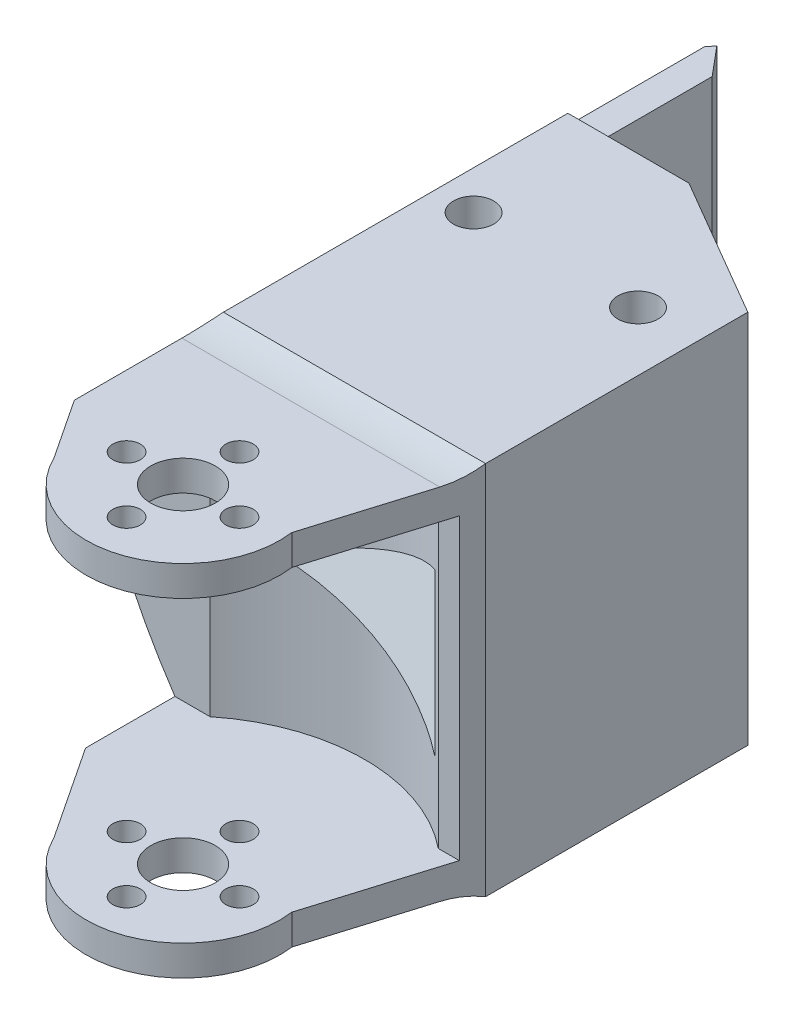
SolidWorks part; units mm, degrees
ref_plane "Front Plane" through (0, 0, 0) normal (0, 0, 1) x (1, 0, 0)
ref_plane "Top Plane" through (0, 0, 0) normal (0, 1, 0) x (1, 0, 0)
ref_plane "Right Plane" through (0, 0, 0) normal (1, 0, 0) x (0, 0, -1)
sketch "Sketch2" plane through (0, 0, 0) normal (0, 1, 0) x (1, 0, 0)
  line L0 (17.5, 0) -> (17.5, 37.7)
  line L1 (-15, 2.5) -> (15, 2.5)
  line L2 (-15, 2.5) -> (-15, 37.7)
  line L4 (15, 2.5) -> (15, 37.7)
  line L5 (17.5, 37.7) -> (15, 37.7)
  line L7 (-17.5, 37.7) -> (-17.5, 0)
  line L8 (-17.5, 0) -> (17.5, 0)
  line L10 (-17.5, 37.7) -> (-15, 37.7)
  point P4 (0, 2.5)
  point P12 (0, 0)
  dimension "D1" = 2.5
  dimension "D2" = 2.5
  dimension "D3" = 37.7
  dimension "D4" = 30
  dimension "D5" = 15
extrude "Boss-Extrude1" add sketch "Sketch2" along normal blind 32.5
sketch "Sketch4" plane through (0, 0, 0) normal (0, -1, 0) x (1, 0, 0)
  line L0 (-17.5, 0) -> (-17.5, -7.4438)
  line L8 (17.5, -7.4438) -> (17.5, 0)
  line L9 (17.5, 0) -> (-17.5, 0)
  line L10 (17.5, 0) -> (17.5, -37.7) construction
  line L13 (-17.5, -7.4438) -> (-17.5, -37.7)
  line L23 (-17.5, -37.7) -> (-15, -37.7)
  line L34 (-15, -37.7) -> (-15, -7.5)
  line L35 (-15, -2.5) -> (-15, -37.7) construction
  line L36 (-15, -7.5) -> (15, -7.5)
  line L37 (15, -37.7) -> (15, -2.5) construction
  line L38 (15, -7.5) -> (15, -37.7)
  line L39 (15, -37.7) -> (17.5, -37.7)
  line L40 (17.5, -37.7) -> (17.5, -7.4438)
  circle A2 centre (-10.1889, -4.95) radius 1.05
  circle A5 centre (10.1889, -4.95) radius 1.05
  dimension "D5" = 2.1
  dimension "D1" = 7.5
  dimension "D6" = 7.3111
  dimension "D7" = 4.95
  dimension "D8" = 7.3111
extrude "Boss-Extrude2" add sketch "Sketch4" along normal blind 2
sketch "Sketch7" plane through (0, -2, 0) normal (0, -1, 0) x (1, 0, 0)
  line L0 (-17.5, 0) -> (-17.5, -37.7)
  line L1 (-17.5, -37.7) -> (-15, -37.7)
  line L2 (-17.5, 0) -> (17.5, 0)
  line L4 (17.5, 0) -> (17.5, -37.7)
  line L5 (17.5, -37.7) -> (15, -37.7)
  line L6 (15, -37.7) -> (15, -7.5)
  line L7 (15, -7.5) -> (-15, -7.5)
  line L8 (-15, -7.5) -> (-15, -37.7)
  circle A2 centre (-10.1889, -4.95) radius 2.495
  circle A3 centre (10.1889, -4.95) radius 2.495
  dimension "D1" = 4.99
extrude "Wire spacing2" add sketch "Sketch7" along normal blind 3
sketch "Sketch8" plane through (0, -5, 0) normal (0, -1, 0) x (1, 0, 0)
  line L0 (-17.5, 0) -> (-17.5, -37.7)
  line L1 (-17.5, -37.7) -> (17.5, -37.7)
  line L2 (17.5, -37.7) -> (17.5, 0) construction
  line L3 (15, -37.7) -> (17.5, -37.7) construction
  line L4 (-17.5, 0) -> (17.5, 0)
  line L6 (17.5, 0) -> (17.5, -37.7)
  circle A0 centre (-10.1889, -4.95) radius 2.495
  circle A1 centre (10.1889, -4.95) radius 2.495
  circle A2 centre (10.1889, -4.95) radius 2.495 construction
  circle A3 centre (-10.1889, -4.95) radius 2.495 construction
extrude "Boss-Extrude6" add sketch "Sketch8" along normal blind 2
sketch "Sketch5" plane through (0, 32.5, 0) normal (0, 1, 0) x (1, 0, 0)
  line L0 (-7.439, 10) -> (-7.439, 2.5)
  line L9 (15, 2.5) -> (-15, 2.5) construction
  line L11 (-10.1889, 12) -> (-7.439, 10)
  line L13 (-17.5, 0) -> (17.5, 0) construction
  line L15 (-17.5, 0) -> (-17.5, 37.7)
  line L17 (10.1889, 12) -> (7.439, 10)
  line L20 (17.5, 0) -> (17.5, 37.7)
  line L21 (-7.439, 2.5) -> (7.439, 2.5)
  line L22 (7.439, 2.5) -> (7.439, 10)
  line L23 (-17.5, 0) -> (17.5, 0)
  line L24 (-10.1889, 12) -> (-15, 12)
  line L25 (-15, 37.7) -> (-15, 7.5) construction
  line L26 (-15, 12) -> (-15, 37.7)
  line L27 (-15, 37.7) -> (-17.5, 37.7)
  line L30 (17.5, 37.7) -> (15, 37.7)
  line L31 (15, 37.7) -> (15, 12)
  line L32 (15, 7.5) -> (15, 37.7) construction
  line L33 (15, 12) -> (10.1889, 12)
  circle A0 centre (-10.1889, 4.95) radius 1.05 construction
  circle A1 centre (-10.1889, 8.7) radius 1.05
  circle A2 centre (10.1889, 8.7) radius 1.05
  circle A3 centre (10.1889, 4.95) radius 1.05 construction
  dimension "D4" = 0
  dimension "D7" = 8.7
  dimension "D3" = 0
  dimension "D1" = 12
  dimension "D2" = 10.061
  dimension "D5" = 10
  dimension "D6" = 10.061
extrude "Boss-Extrude3" add sketch "Sketch5" along normal blind 2
sketch "Sketch9" plane through (0, 34.5, 0) normal (0, 1, 0) x (1, 0, 0)
  line L0 (-17.5, 0) -> (-17.5, 37.7)
  line L1 (-17.5, 37.7) -> (-15, 37.7)
  line L2 (-15, 37.7) -> (-15, 12)
  line L3 (-15, 12) -> (-10.1889, 12)
  line L4 (-10.1889, 12) -> (-7.439, 10)
  line L5 (-7.439, 10) -> (-7.439, 2.5)
  line L6 (-7.439, 2.5) -> (7.439, 2.5)
  line L7 (7.439, 2.5) -> (7.439, 10)
  line L8 (7.439, 10) -> (10.1889, 12)
  line L9 (10.1889, 12) -> (7.439, 10) construction
  line L10 (10.1889, 12) -> (15, 12)
  line L11 (15, 7.5) -> (15, 37.7) construction
  line L12 (15, 12) -> (15, 37.7)
  line L13 (15, 37.7) -> (17.5, 37.7)
  line L14 (17.5, 0) -> (17.5, 37.7) construction
  line L15 (17.5, 37.7) -> (15, 37.7) construction
  line L16 (17.5, 37.7) -> (17.5, 0)
  line L17 (17.5, 0) -> (-17.5, 0)
  line L18 (15, 12) -> (10.1889, 12) construction
  circle A0 centre (-10.1889, 8.7) radius 2.495
  circle A1 centre (10.1889, 8.7) radius 2.495
  dimension "D1" = 4.99
  dimension "D2" = 0
extrude "Wire spacing1" add sketch "Sketch9" along normal blind 3
sketch "Sketch10" plane through (0, 37.5, 0) normal (0, 1, 0) x (1, 0, 0)
  line L1 (-17.5, 37.7) -> (17.5, 37.7)
  line L2 (-17.5, 37.7) -> (-17.5, 0)
  line L3 (-17.5, 0) -> (17.5, 0)
  line L4 (17.5, 37.7) -> (17.5, 0)
  circle A0 centre (-10.1889, 8.7) radius 2.495
  circle A1 centre (10.1889, 8.7) radius 2.495
  circle A2 centre (-10.1889, 8.7) radius 2.495 construction
  circle A3 centre (10.1889, 8.7) radius 2.495 construction
extrude "Boss-Extrude8" add sketch "Sketch10" along normal blind 2
sketch "Sketch11" plane through (0, 39.5, 0) normal (0, 1, 0) x (1, 0, 0)
  line L0 (17.5, 37.7) -> (-17.5, 37.7) construction
  circle A0 centre (0, 37.7) radius 12.5
  dimension "D1" = 25
extrude "Cut-Extrude1" cut sketch "Sketch11" against normal through all
sketch "Sketch12" plane through (0, -7, 0) normal (0, -1, 0) x (1, 0, 0)
  line L4 (0, -25.2) -> (17.5, -15)
  line L5 (17.5, -37.7) -> (17.5, 0) construction
  line L6 (17.5, -15) -> (17.5, -47.4845)
  line L7 (17.5, -47.4845) -> (0, -25.2)
  line L8 (17.5, 0) -> (-17.5, 0) construction
  arc A1 (12.5, -37.7) -> (-12.5, -37.7) centre (0, -37.7) ccw construction
  dimension "D1" = 15
extrude "Cut-Extrude2" cut sketch "Sketch12" against normal through all
sketch "Sketch13" plane through (0, 0, 0) normal (0, 0, 1) x (1, 0, 0)
  line L0 (17.5, -7) -> (-17.5, -7) construction
  line L1 (17.5, 39.5) -> (-27.5, 39.5)
  line L2 (17.5, 39.5) -> (17.5, -7)
  line L3 (17.5, -7) -> (-27.5, -7)
  line L4 (-27.5, 39.5) -> (-27.5, -7)
  line L5 (-17.5, 39.5) -> (-17.5, -7) construction
  dimension "D1" = 10
extrude "Boss-Extrude9" add sketch "Sketch13" along normal blind 17.5
sketch "Sketch15" plane through (0, 0, 0) normal (0, 0, -1) x (-1, 0, 0)
  line L0 (17.5, -7) -> (12.5, -7) construction
  line L1 (27.5, 39.5) -> (15, 39.5)
  line L2 (27.5, 39.5) -> (27.5, -7)
  line L3 (27.5, -7) -> (15, -7)
  line L4 (15, 39.5) -> (15, -7)
extrude "Boss-Extrude10" add sketch "Sketch15" along normal blind 50
sketch "Sketch18" plane through (0, -7, 0) normal (0, -1, 0) x (1, 0, 0)
  line L0 (12.5, 22.5) -> (12.5, 17.5)
  line L1 (12.5, 17.5) -> (-12.5, 17.5)
  line L2 (-12.5, 22.5) -> (-12.5, 17.5)
  line L3 (12.5, 22.5) -> (9.3675, 30)
  line L4 (-9.3675, 30) -> (-12.5, 22.5)
  line L5 (-27.5, 17.5) -> (17.5, 17.5) construction
  circle A0 centre (0, 37.5) radius 4
  arc A1 (9.3675, 30) -> (-9.3675, 30) centre (0, 37.5) ccw
  circle A2 centre (0, 30.5) radius 1.7
  circle A3 centre (-7, 37.5) radius 1.7
  circle A4 centre (0, 44.5) radius 1.7
  circle A5 centre (7, 37.5) radius 1.7
  point P11 (7.7726, 26.3901)
  point P12 (0, 17.5)
  dimension "D3" = 8
  dimension "D5" = 12
  dimension "D7" = 3.4
  dimension "D1" = 25
  dimension "D2" = 20
  dimension "D4" = 5
  dimension "D6" = 12.5
  dimension "D8" = 7
  dimension "D9" = 7
  dimension "D10" = 7
  dimension "D11" = 7
  dimension "D12" = 0
  dimension "D13" = 0
extrude "Boss-Extrude11" add sketch "Sketch18" against normal up to surface (46.5 mm away) up to face at (-8.1361, 39.5, -22.2514)
sketch "Sketch22" plane through (0, -7, 0) normal (0, -1, 0) x (1, 0, 0)
  line L0 (-27.5, 17.5) -> (-9, 45.4373)
  line L1 (-9, 45.4373) -> (-9, 17.5)
  line L2 (-9, 17.5) -> (-27.5, 17.5)
  line L4 (17.5, 17.5) -> (9, 45.4373)
  line L5 (9, 45.4373) -> (9, 17.5)
  line L6 (9, 17.5) -> (17.5, 17.5)
  arc A0 (9.3675, 30) -> (-9.3675, 30) centre (0, 37.5) ccw construction
  circle A1 centre (-7, 37.5) radius 1.7 construction
  circle A2 centre (7, 37.5) radius 1.7 construction
  dimension "D1" = 2
  dimension "D2" = 2
extrude "Boss-Extrude13" add sketch "Sketch22" against normal up to surface (46.5 mm away) up to face at (-4.6492, 39.5, -1.3222)
sketch "Sketch21" plane through (-27.5, 0, 0) normal (-1, 0, 0) x (0, 0, 1)
  line L1 (107.4125, 34.75) -> (17.5, 34.75)
  line L2 (107.4125, 34.75) -> (107.4125, -2.25)
  line L3 (107.4125, -2.25) -> (17.5, -2.25)
  line L4 (17.5, 34.75) -> (17.5, -2.25)
  line L6 (-50, -7) -> (-50, 39.5) construction
  line L7 (17.5, 39.5) -> (17.5, -7) construction
  point P6 (-50, 16.25)
  point P7 (17.5, 16.25)
  dimension "D1" = 37
  dimension "D2" = 0
extrude "Cut-Extrude3" cut sketch "Sketch21" against normal through all
sketch "Sketch26" plane through (0, 39.5, 0) normal (0, 1, 0) x (1, 0, 0)
  line L0 (-27.5, -17.5) -> (-27.5, 50) construction
  line L1 (-27.5, 29.3872) -> (-27.5, 50)
  line L2 (-27.5, 50) -> (-15, 50)
  spline S0 degree 2 poles (-15, 50) (-23.5947, 41.1535) (-27.5, 29.3872) knots 0 0 0 1 1 1
extrude "Cut-Extrude5" cut sketch "Sketch26" against normal through all
sketch "Sketch24" plane through (0, 0, 0) normal (0, 0, -1) x (-1, 0, 0)
  line L4 (15, -7) -> (27.5, -7)
  line L5 (27.5, -7) -> (27.5, 16.25)
  spline S0 degree 2 poles (27.5, 16.25) (23.3985, 3.4824) (15, -7) knots 0 0 0 1 1 1
extrude "Cut-Extrude4" cut sketch "Sketch24" against normal through all both and the other way through all
ref_plane "Plane1" through (0, 16.25, 0) normal (0, -1, 0) x (-1, 0, 0)
mirror "Mirror1" about plane through (0, 16.25, 0) normal (0, -1, 0) of "Cut-Extrude4"
sketch "Sketch27" plane through (0, 0, -2.5) normal (0, 0, -1) x (-1, 0, 0)
  line L0 (-12.5, 26.25) -> (8.9451, 16.25)
  line L1 (-24.75, 16.25) -> (24.75, 16.25) construction
  line L2 (8.9451, 16.25) -> (-12.5, 6.25)
  line L4 (-12.5, 6.25) -> (-12.5, 26.25)
  line L5 (-15, 32.5) -> (-15, 0) construction
  point P7 (-12.5, 16.25)
  dimension "D1" = 50
  dimension "D2" = 20
  dimension "D3" = 2.5
extrude "Cut-Extrude6" cut sketch "Sketch27" against normal through all
sketch "Sketch28" plane through (0, 39.5, 0) normal (0, 1, 0) x (1, 0, 0)
  line L0 (-15, 37.7) -> (-15, 50)
  line L1 (-15, 50) -> (-10, 50)
  line L2 (-10, 50) -> (-10, 47.127)
  line L3 (-10, 47.127) -> (-12.5, 47.127)
  line L4 (-12.5, 47.127) -> (-12.5, 37.7)
  line L5 (-15, 37.7) -> (-12.5, 37.7)
  dimension "D1" = 2.5
extrude "Boss-Extrude14" add sketch "Sketch28" against normal up to surface (46.5 mm away) up to face at (-0.7656, -7, 3.6462)
fillet "Fillet2" radius 10 1 edges at (-15, 16.25, -50)
sketch "Sketch29" plane through (0, 0, -37.7) normal (0, 0, 1) x (1, 0, 0)
  line L1 (-15, 37.5) -> (-12.5, 37.5)
  line L2 (-15, 37.5) -> (-15, -5)
  line L3 (-15, -5) -> (-12.5, -5)
  line L4 (-12.5, 37.5) -> (-12.5, -5)
extrude "Cut-Extrude8" cut sketch "Sketch29" against normal up to surface (9.427 mm away) up to face at (-11.25, 16.25, -47.127)
fillet "Fillet3" radius 1 1 edges at (-10, 16.25, -47.127)
sketch "Sketch33" plane through (0, 0, -50) normal (0, 0, -1) x (-1, 0, 0)
  line L1 (0, 39.5) -> (21.955, 39.5)
  line L2 (0, 39.5) -> (0, 34.5)
  line L3 (0, 34.5) -> (21.955, 34.5)
  line L4 (21.955, 39.5) -> (21.955, 34.5)
  line L5 (0, -7) -> (23.3737, -7)
  line L6 (0, -7) -> (0, -2)
  line L7 (0, -2) -> (23.3737, -2)
  line L8 (23.3737, -7) -> (23.3737, -2)
  dimension "D1" = 5
  dimension "D2" = 5
extrude "Cut-Extrude13" cut sketch "Sketch33" against normal up to vertex (24.8 mm away) up to point (0, 39.5, -25.2)
sketch "Sketch34" plane through (0, 34.5, 0) normal (0, 1, 0) x (1, 0, 0)
  line L0 (0, 25.2) -> (-17.9905, 46.6483)
  line L1 (-17.9905, 46.6483) -> (-19.0359, 53.4266)
  line L2 (-19.0359, 53.4266) -> (0, 53.4266)
  line L3 (0, 53.4266) -> (0, 25.2)
extrude "Cut-Extrude14" cut sketch "Sketch34" against normal through all both and the other way through all
sketch "Sketch36" plane through (17.5, 0, 0) normal (1, 0, 0) x (0, 0, -1)
  line L1 (-17.5, 39.5) -> (-49.5, 39.5)
  line L2 (-17.5, 39.5) -> (-17.5, 38.5)
  line L3 (-17.5, 38.5) -> (-49.5, 38.5)
  line L4 (-49.5, 39.5) -> (-49.5, 38.5)
  line L6 (-17.5, -7) -> (-49.5, -7)
  line L7 (-17.5, -7) -> (-17.5, -6)
  line L8 (-17.5, -6) -> (-49.5, -6)
  line L9 (-49.5, -7) -> (-49.5, -6)
  dimension "D1" = 1
extrude "Cut-Extrude15" cut sketch "Sketch36" against normal through all both and the other way through all
fillet "Fillet4" radius 10 2 edges at (0.8563, -6, 17.5) (0.8563, 38.5, 17.5)
sketch "Sketch37" plane through (0, 0, -2.5) normal (0, 0, -1) x (-1, 0, 0)
  line L0 (-15, 37.5) -> (-15, -5) construction
  line L1 (-15, 27.9049) -> (15, 27.9049)
  line L2 (-15, 27.9049) -> (-15, 4.6789)
  line L3 (-15, 4.6789) -> (15, 4.6789)
  line L4 (15, 27.9049) -> (15, 4.6789)
  line L5 (15, -2) -> (15, 34.5) construction
extrude "Cut-Extrude16" cut sketch "Sketch37" against normal blind 5 and the other way through all
sketch "Sketch38" plane through (0, 0, -2.5) normal (0, 0, -1) x (-1, 0, 0)
  line L1 (-7.439, 37.5) -> (7.439, 37.5)
  line L2 (-7.439, 37.5) -> (-7.439, -2.25)
  line L3 (-7.439, -2.25) -> (7.439, -2.25)
  line L4 (7.439, 37.5) -> (7.439, -2.25)
  line L8 (-17.5, -2.25) -> (18.5058, -2.25) construction
extrude "Cut-Extrude17" cut sketch "Sketch38" against normal blind 5
ref_axis "Axis1" through (0, 38.5, 37.5) along (0, -1, 0)
ref_axis "Axis2" through (7, 38.5, 37.5) along (0, -1, 0)
ref_axis "Axis3" through (0, 38.5, 44.5) along (0, -1, 0)
ref_plane "Plane2" through (0, 0, 0) normal (1, 0, 0) x (0, 0, -1)
ref_plane "Plane3" through (0, 0, 37.5) normal (0, 0, -1) x (-1, 0, 0)
ref_plane "Plane5" through (0, 16.25, 0) normal (0, 1, 0) x (1, 0, 0)
sketch "Sketch39" plane through (0, 0, 17.5) normal (0, 0, 1) x (1, 0, 0)
  line L0 (17.5, -2.25) -> (17.5, 34.75)
  line L1 (17.5, 34.75) -> (-18.5058, 34.75)
  line L2 (17.5, -2.25) -> (-18.5058, -2.25)
  line L3 (12.5, 6.25) -> (12.5, 26.25)
  line L4 (12.5, 26.25) -> (12.5, 6.25) construction
  line L5 (12.5, 26.25) -> (-8.9451, 16.25)
  line L6 (-8.9451, 16.25) -> (12.5, 6.25)
  parabola Q0 (-27.5, 16.25) -> (-18.5058, 34.75) focus (9.1255, 11.3542) apex (-22.4768, 28.161) construction
  parabola Q1 (-27.5, 16.25) -> (-18.5058, -2.25) focus (9.1255, 21.1458) apex (-22.4768, 4.339) construction
  spline S0 degree 2 poles (-18.5058, 34.75) (-24.3234, 26.1586) (-27.5, 16.25) knots 0 0 0 1 1 1
  spline S1 degree 2 poles (-18.5058, -2.25) (-24.3299, 6.3567) (-27.5, 16.25) knots 0 0 0 1 1 1
extrude "Boss-Extrude15" add sketch "Sketch39" along normal blind 2.5
sketch "Sketch40" plane through (0, -2.25, 0) normal (0, 1, 0) x (1, 0, 0)
  circle A0 centre (0, -37.5) radius 22.5
  circle A1 centre (0, -37.5) radius 4 construction
  dimension "D1" = 45
extrude "Cut-Extrude19" cut sketch "Sketch40" along normal up to surface (37 mm away) up to face at (-7, 34.75, 39.2)
sketch "Sketch41" plane through (0, 39.5, 0) normal (0, 1, 0) x (1, 0, 0)
  line L0 (17.5, -20) -> (17.5, -17.5)
  line L1 (17.5, -17.5) -> (16.7394, -20) construction
  line L2 (16.1738, -21.8589) -> (17.5, -17.5) construction
  line L3 (17.5, -17.5) -> (16.7394, -20)
  line L4 (16.7394, -20) -> (17.5, -20)
extrude "Cut-Extrude20" cut sketch "Sketch41" against normal through all both and the other way through all
sketch "Sketch42" plane through (0, 0, -7.5) normal (0, 0, -1) x (-1, 0, 0)
  line L0 (15, -5) -> (-15, -5) construction
  line L5 (7.439, 4.6789) -> (-7.439, 4.6789)
  line L6 (7.439, 4.6789) -> (7.439, -5)
  line L7 (7.439, -5) -> (-7.439, -5)
  line L8 (-7.439, 4.6789) -> (-7.439, -5)
  line L9 (-7.439, 4.6789) -> (-7.439, 0) construction
  dimension "D1" = 0
extrude "Cut-Extrude21" cut sketch "Sketch42" against normal up to surface (10 mm away) up to face at (5.3516, 16.25, 2.5)
